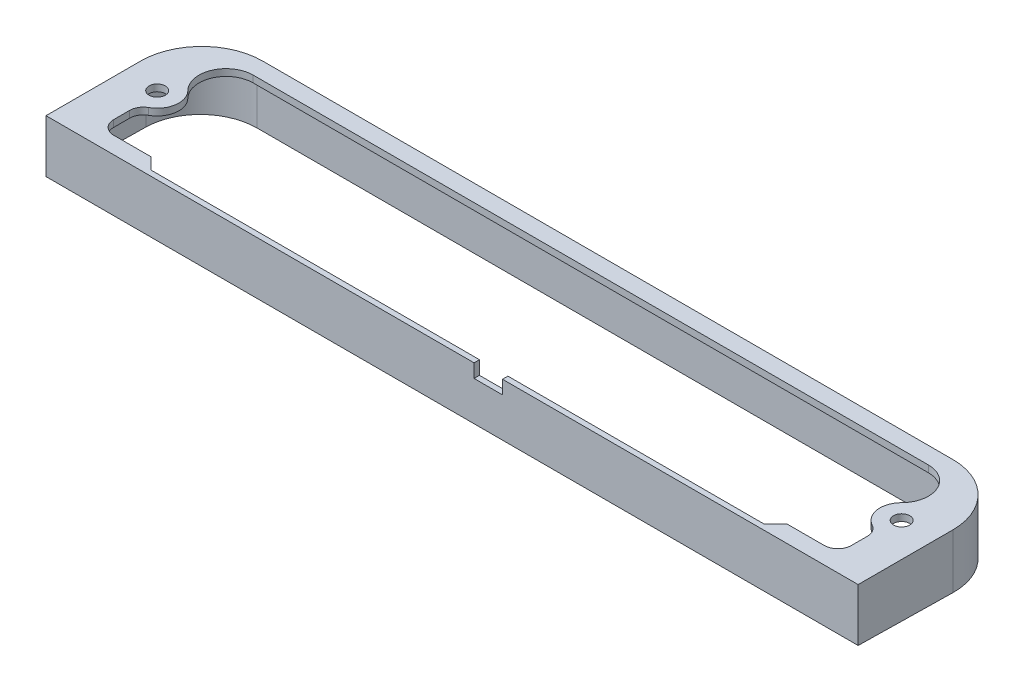
SolidWorks part; units mm, degrees
material "ABS"
ref_plane "Front" through (0, 0, 0) normal (0, 0, 1) x (1, 0, 0)
ref_plane "Top" through (0, 0, 0) normal (0, 1, 0) x (1, 0, 0)
ref_plane "Right" through (0, 0, 0) normal (1, 0, 0) x (0, 0, -1)
ref_axis "X" through (-80.9, 0, 0) along (1, 0, 0)
ref_axis "Y" through (0, -50, 0) along (0, 1, 0)
ref_axis "Z" through (0, 0, -80.9) along (0, 0, 1)
sketch "Sketch1" plane through (0, 0, 0) normal (0, 1, 0) x (1, 0, 0)
  line L0 (-60, 0) -> (-54.5, 0)
  line L2 (-49.8878, 20.5) -> (49.8878, 20.5)
  line L4 (54.5, 0) -> (60, 0)
  line L5 (60, 0) -> (60, 14)
  line L6 (51, 23) -> (-51, 23)
  line L7 (-60, 14) -> (-60, 0)
  line L8 (-54.5, 0) -> (54.5, 0)
  line L9 (-47, 0.8) -> (47, 0.8)
  line L10 (-54.5, 0) -> (-54.5, 0.8) construction
  line L11 (54.5, 0) -> (54.5, 0.8) construction
  line L12 (55, 11.43) -> (-55, 11.43) construction
  line L13 (0, 11.43) -> (0, 0) construction
  line L14 (54.5, 2.5) -> (47, 2.5)
  line L15 (47, 2.5) -> (47, 0.8)
  line L16 (-54.5, 2.5) -> (-47, 2.5)
  line L17 (-47, 2.5) -> (-47, 0.8)
  line L18 (-54.5, 0.8) -> (-54.5, 2.5) construction
  line L19 (-54.5, 0.8) -> (-47, 0.8) construction
  line L20 (54.5, 2.5) -> (54.5, 0.8) construction
  line L21 (47, 0.8) -> (54.5, 0.8) construction
  line L22 (54.5, 8.2693) -> (54.5, 2.5)
  line L23 (-54.5, 2.5) -> (-54.5, 8.2693)
  arc A0 (-52.7279, 13.6833) -> (-49.8878, 20.5) centre (-49.8878, 16.5) cw
  arc A1 (49.8878, 20.5) -> (52.7279, 13.6833) centre (49.8878, 16.5) cw
  arc A2 (60, 14) -> (51, 23) centre (51, 14) ccw
  arc A3 (-51, 23) -> (-60, 14) centre (-51, 14) ccw
  circle A4 centre (55, 11.43) radius 1.2
  circle A5 centre (-55, 11.43) radius 1.2
  arc A6 (52.7279, 13.6833) -> (54.5, 8.2693) centre (55, 11.43) ccw
  arc A7 (-52.7279, 13.6833) -> (-54.5, 8.2693) centre (-55, 11.43) cw
  point P7 (-45.2309, 0.8)
  dimension "D5" = 9
  dimension "D6" = 4
  dimension "D10" = 2.4
  dimension "D13" = 3.2
  dimension "D1" = 120
  dimension "D2" = 5.5
  dimension "D3" = 2.5
  dimension "D4" = 23
  dimension "D7" = 0.8
  dimension "D8" = 11.43
  dimension "D9" = 110
  dimension "D11" = 13
  dimension "D12" = 2.5
extrude "Boss-Extrude1" add sketch "Sketch1" along normal blind 1
sketch "Sketch8" plane through (0, 0, 0) normal (0, -1, 0) x (-1, 0, 0)
  line L0 (-59.2, 0.8) -> (59.2, 0.8)
  line L1 (59.2, 0.8) -> (59.2, 14)
  line L2 (51, 22.2) -> (-51, 22.2)
  line L3 (-59.2, 14) -> (-59.2, 0.8)
  line L4 (60, 0) -> (60, 14)
  line L5 (51, 23) -> (-51, 23)
  line L6 (-60, 14) -> (-60, 0)
  line L7 (-60, 0) -> (60, 0)
  line L8 (60, 0) -> (60, 14)
  line L9 (51, 23) -> (-51, 23)
  line L10 (-60, 14) -> (-60, 0)
  line L11 (-60, 0) -> (60, 0)
  arc A0 (59.2, 14) -> (51, 22.2) centre (51, 14) ccw
  arc A1 (-51, 22.2) -> (-59.2, 14) centre (-51, 14) ccw
  arc A2 (60, 14) -> (51, 23) centre (51, 14) ccw
  arc A3 (-51, 23) -> (-60, 14) centre (-51, 14) ccw
  arc A4 (60, 14) -> (51, 23) centre (51, 14) ccw
  arc A5 (-51, 23) -> (-60, 14) centre (-51, 14) ccw
  dimension "D1" = 0
  dimension "D2" = 0.8
extrude "Boss-Extrude2" add sketch "Sketch8" along normal blind 8.2 from surface starting at face at (55, 1, -10.23)
chamfer "Chamfer1" distance 1 angle 45 7 edges at (59.2, 0, -7.4) (56.7983, 0, -19.7983) (-59.2, 0, -7.4) (-56.7983, 0, -19.7983) (53.1, 0, -0.8) (-53.1, 0, -0.8) (0, 0, -22.2)
sketch "Sketch9" plane through (0, 0, 0) normal (1, 0, 0) x (0, 0, -1)
  line L0 (-2, -7.2) -> (23, -7.2)
  line L1 (23, -7.2) -> (-2, -6.7636)
  line L3 (-2, -6.7636) -> (-2, -7.2)
  dimension "D1" = 25
  dimension "D2" = 1
extrude "Cut-Extrude1" cut sketch "Sketch9" against normal through all both and the other way through all
sketch "Sketch11" plane through (0, 0, 0) normal (0, 0, 1) x (1, 0, 0)
  line L0 (3.25, 1) -> (3.25, -1)
  line L1 (-60, 1) -> (60, 1) construction
  line L2 (3.25, -1) -> (7.45, -1)
  line L3 (7.45, -1) -> (7.45, 1)
  line L4 (7.45, 1) -> (3.25, 1)
  line L5 (5.35, -1) -> (5.35, 1) construction
  line L7 (60, 1) -> (60, -6.7985) construction
  dimension "D1" = 54.65
  dimension "D2" = 4.2
  dimension "D3" = 2
extrude "Cut-Extrude2" cut sketch "Sketch11" against normal up to next
fillet "Fillet1" radius 2 4 edges at (-54.5, 0.5, -8.2693) (-54.5, 0.5, -2.5) (54.5, 0.5, -2.5) (54.5, 0.5, -8.2693)
chamfer "Chamfer2" distance 1.7 angle 45 2 edges at (-47, 0, -0.8) (47, 0, -0.8)
